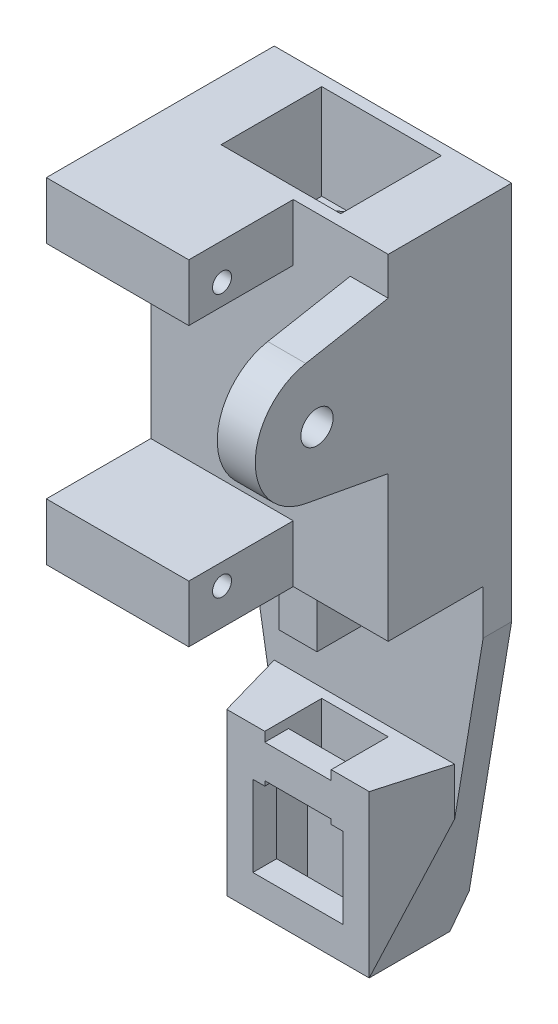
SolidWorks part; units mm, degrees
ref_plane "Plano frontal" through (0, 0, 0) normal (0, 0, 1) x (1, 0, 0)
ref_plane "Plano superior" through (0, 0, 0) normal (0, 1, 0) x (1, 0, 0)
ref_plane "Plano direito" through (0, 0, 0) normal (1, 0, 0) x (0, 0, -1)
sketch "Esboço1" plane through (0, 0, 0) normal (0, 0, 1) x (1, 0, 0)
  line L0 (-12.5, 0) -> (12.5, 0)
  line L1 (12.5, 0) -> (12.5, -40)
  line L2 (12.5, -40) -> (7.5, -70)
  line L3 (7.5, -70) -> (-7.5, -70)
  line L4 (-7.5, -70) -> (-12.5, -40)
  line L5 (-12.5, -40) -> (-12.5, 0)
  point P3 (0, -70)
  point P7 (0, 0)
  dimension "D1" = 40
  dimension "D2" = 30
  dimension "D3" = 25
  dimension "D4" = 15
extrude "Ressalto-extrusão1" add sketch "Esboço1" along normal blind 13
sketch "Esboço2" plane through (0, 0, 13) normal (0, 0, 1) x (1, 0, 0)
  line L1 (2.5, -35.3) -> (-12.5, -35.3)
  line L2 (2.5, -35.3) -> (2.5, -29.3)
  line L3 (2.5, -29.3) -> (-12.5, -29.3)
  line L4 (-12.5, -35.3) -> (-12.5, -29.3)
  line L5 (-12.5, 0) -> (2.5, 0)
  line L6 (-12.5, 0) -> (-12.5, -6)
  line L7 (-12.5, -6) -> (2.5, -6)
  line L8 (2.5, 0) -> (2.5, -6)
  line L11 (12.5, -4) -> (8.5, -4)
  line L12 (12.5, -4) -> (12.5, -20)
  line L13 (12.5, -20) -> (8.5, -20)
  line L14 (8.5, -4) -> (8.5, -20)
  line L15 (-12.5, -6) -> (-12.5, -29.3) construction
  line L16 (-12.5, -28.9) -> (-12.5, -6.4) construction
  point P16 (8.5, -12)
  point P21 (-12.5, -17.65)
  dimension "D1" = 23.3
  dimension "D2" = 6
  dimension "D3" = 15
  dimension "D4" = 21
  dimension "D6" = 22.5
  dimension "D7" = 5.65
  dimension "D8" = 16
  dimension "D9" = 4
extrude "Ressalto-extrusão2" add sketch "Esboço2" along normal blind 15
sketch "Esboço3" plane through (2.5, 0, 0) normal (1, 0, 0) x (0, 0, -1)
  line L0 (-28, -6) -> (-28, -29.3) construction
  line L1 (-28, -17.65) -> (-13, -17.65) construction
  line L2 (-13, -40) -> (-13, -20) construction
  line L3 (-28, -6) -> (-13, -6) construction
  line L4 (-28, 0) -> (-9, 0) construction
  line L5 (-28, 0) -> (-13, 0) construction
  line L6 (-28, -20) -> (-28, -4) construction
  circle A0 centre (-20.5, -3.8) radius 1
  circle A3 centre (-20.5, -31.5) radius 1
  circle A5 centre (-20.5, -12) radius 1.75
  point P24 (-20.5, -6)
  point P31 (-28, -12)
  dimension "D1" = 2
  dimension "D5" = 3.5
  dimension "D2" = 27.7
extrude "Corte-extrusão1" cut sketch "Esboço3" against normal through all contours A5 | A0 | A3 region at (2.5, -3.8, 20.5) region at (2.5, -12, 20.5)
sketch "Esboço10" plane through (12.5, 0, 0) normal (1, 0, 0) x (0, 0, -1)
  line L0 (-28, -20) -> (-28, -4) construction
  line L1 (-20.5, -3.8) -> (-20.5, -31.5) construction
  line L2 (-13, -4) -> (-28, -4)
  line L3 (-28, -4) -> (-28, -20)
  line L4 (-28, -20) -> (-13, -20)
  line L5 (-13, -4) -> (-21.684, -5.6087)
  line L6 (-13, -20) -> (-21.684, -18.3913)
  circle A0 centre (-20.5, -12) radius 1.7
  arc A2 (-21.684, -5.6087) -> (-21.684, -18.3913) centre (-20.5, -12) ccw
  point P5 (-28, -12)
  dimension "D1" = 3.4
  dimension "D2" = 6.5
extrude "Corte-extrusão4" cut sketch "Esboço10" against normal blind 10
sketch "Esboço11" plane through (0, 0, 13) normal (0, 0, 1) x (1, 0, 0)
  line L0 (12.5, -40) -> (12.5, -20) construction
  line L1 (-12.5, -35.3) -> (12.5, -35.3)
  line L2 (-12.5, -35.3) -> (-12.5, -70)
  line L3 (-12.5, -70) -> (12.5, -70)
  line L4 (12.5, -35.3) -> (12.5, -70)
  line L5 (-7.5, -70) -> (7.5, -70) construction
extrude "Corte-extrusão5" cut sketch "Esboço11" against normal blind 10
sketch "Esboço6" plane through (0, -70, 0) normal (0, -1, 0) x (1, 0, 0)
  line L0 (-5, 4) -> (-5, 7.5)
  line L1 (-5, 7.5) -> (-4.75, 7.5)
  line L2 (-4.75, 7.5) -> (-4.75, 10)
  line L3 (-4.75, 10) -> (-7.5, 10)
  line L4 (-7.5, 10) -> (-7.5, 3)
  line L7 (0, 13) -> (0, 11.0668) construction
  line L8 (-7.5, 13) -> (7.5, 13) construction
  line L10 (7.5, 10) -> (7.5, 3)
  line L11 (4.75, 10) -> (7.5, 10)
  line L12 (4.75, 7.5) -> (4.75, 10)
  line L13 (5, 7.5) -> (4.75, 7.5)
  line L14 (5, 4) -> (5, 7.5)
  line L15 (-7.5, 3) -> (7.5, 3)
  line L16 (5, 4) -> (-5, 4)
  dimension "D2" = 9.5
  dimension "D3" = 3.5
  dimension "D4" = 1
  dimension "D5" = 6
  dimension "D6" = 10
extrude "Ressalto-extrusão3" add sketch "Esboço6" against normal blind 17
sketch "Esboço7" plane through (0, 0, 3) normal (0, 0, 1) x (1, 0, 0)
  line L0 (-7.5, -70) -> (7.5, -70) construction
  line L1 (2, -38) -> (-2, -38)
  line L2 (2, -38) -> (2, -43)
  line L3 (2, -43) -> (-2, -43)
  line L4 (-2, -38) -> (-2, -43)
  line L5 (2, -38) -> (-2, -43) construction
  line L6 (2, -43) -> (-2, -38) construction
  line L7 (-7.5, -53) -> (-5, -53) construction
  line L8 (5, -53) -> (7.5, -53) construction
  line L9 (7.5, -58) -> (3.5, -58)
  line L10 (7.5, -58) -> (7.5, -53)
  line L11 (7.5, -53) -> (3.5, -53)
  line L12 (3.5, -58) -> (3.5, -53)
  line L13 (7.5, -58) -> (3.5, -53) construction
  line L14 (7.5, -53) -> (3.5, -58) construction
  line L15 (-3.5, -58) -> (-7.5, -58)
  line L16 (-3.5, -58) -> (-3.5, -53)
  line L17 (-3.5, -53) -> (-7.5, -53)
  line L18 (-7.5, -58) -> (-7.5, -53)
  line L19 (-3.5, -58) -> (-7.5, -53) construction
  line L20 (-3.5, -53) -> (-7.5, -58) construction
  line L21 (7.5, -53) -> (7.5, -70) construction
  line L22 (7.5, -53) -> (7.5, -70) construction
  line L23 (-7.5, -53) -> (-7.5, -70) construction
  line L24 (-7.5, -53) -> (-7.5, -70) construction
  point P0 (0, -40.5)
  point P5 (-5.5, -55.5)
  point P8 (0, -70)
  point P11 (5.5, -55.5)
  dimension "D1" = 4
  dimension "D2" = 5
  dimension "D3" = 10
  dimension "D4" = 7
  dimension "D5" = 5
  dimension "D6" = 0
extrude "Ressalto-extrusão4" add sketch "Esboço7" along normal up to surface (7 mm away) up to face at (-6.125, -61.5, 10)
sketch "Esboço8" plane through (0, 0, 10) normal (0, 0, 1) x (1, 0, 0)
  line L0 (-7.5, -70) -> (7.5, -70)
  line L1 (7.5, -70) -> (7.5, -66.5)
  line L2 (7.5, -53) -> (7.5, -70) construction
  line L3 (7.5, -66.5) -> (-7.5, -66.5)
  line L4 (-7.5, -53) -> (-7.5, -70) construction
  line L5 (-7.5, -66.5) -> (-7.5, -70)
  line L7 (7.5, -54) -> (-7.5, -54)
  line L8 (7.5, -54) -> (7.5, -57.5)
  line L9 (7.5, -57.5) -> (-7.5, -57.5)
  line L10 (-7.5, -54) -> (-7.5, -57.5)
  dimension "D1" = 3.5
  dimension "D2" = 9
extrude "Ressalto-extrusão5" add sketch "Esboço8" against normal up to surface (2.5 mm away) up to face at (4.875, -64, 7.5)
chamfer "Chanfro2" distance 2 distance2 7 2 edges at (7.5, -61.5, 3) (-7.5, -61.5, 3) first distance on face at (0, -49.575, 3)
chamfer "Chanfro3" distance 1.5 angle 65 1 edges at (0, -70, 0) first distance on face at (0, -70, 5)
sketch "Esboço12" plane through (0, 0, 0) normal (0, 1, 0) x (1, 0, 0)
  line L0 (12.5, -13) -> (12.5, 0) construction
  line L1 (6.3, -11.8) -> (-6.3, -11.8)
  line L2 (6.3, -11.8) -> (6.3, -1.2)
  line L3 (6.3, -1.2) -> (-6.3, -1.2)
  line L4 (-6.3, -11.8) -> (-6.3, -1.2)
  line L5 (6.3, -11.8) -> (-6.3, -1.2) construction
  line L6 (6.3, -1.2) -> (-6.3, -11.8) construction
  point P0 (0, -6.5)
  point P10 (12.5, -6.5)
  dimension "D1" = 10.6
  dimension "D2" = 12.6
extrude "Corte-extrusão6" cut sketch "Esboço12" against normal blind 10
sketch "Esboço13" plane through (0, -10, 0) normal (0, 1, 0) x (1, 0, 0)
  line L0 (-6.3, -1.2) -> (-6.3, -11.8) construction
  line L1 (-6.3, -11.8) -> (6.3, -11.8) construction
  line L2 (-3.4059, -11.8) -> (3.4059, -11.8)
  line L3 (-3.4059, -1.2) -> (3.4059, -1.2)
  line L4 (6.3, -1.2) -> (-6.3, -1.2) construction
  arc A0 (-3.4059, -1.2) -> (-3.4059, -11.8) centre (0, -6.5) ccw
  arc A1 (3.4059, -11.8) -> (3.4059, -1.2) centre (0, -6.5) ccw
  point P5 (-6.3, -6.5)
  point P8 (0, -11.8)
  dimension "D1" = 12.6
  dimension "D2" = 10.6
extrude "Corte-extrusão7" cut sketch "Esboço13" against normal blind 22
sketch "Esboço15" plane through (-12.5, 0, 0) normal (-1, 0, 0) x (0, 0, 1)
  line L0 (0, 0) -> (0, -40) construction
  line L1 (28, 0) -> (0, 0) construction
  circle A0 centre (6, -28) radius 2
  dimension "D1" = 4
  dimension "D2" = 6
  dimension "D3" = 28
extrude "Corte-extrusão9" cut sketch "Esboço15" against normal blind 15
sketch "Esboço17" plane through (0, 0, 28) normal (0, 0, 1) x (1, 0, 0)
  line L1 (2.5, 0) -> (-12.5, 0)
  line L2 (2.5, 0) -> (2.5, -35.3)
  line L3 (2.5, -35.3) -> (-12.5, -35.3)
  line L4 (-12.5, 0) -> (-12.5, -35.3)
extrude "Corte-extrusão10" cut sketch "Esboço17" against normal blind 4
